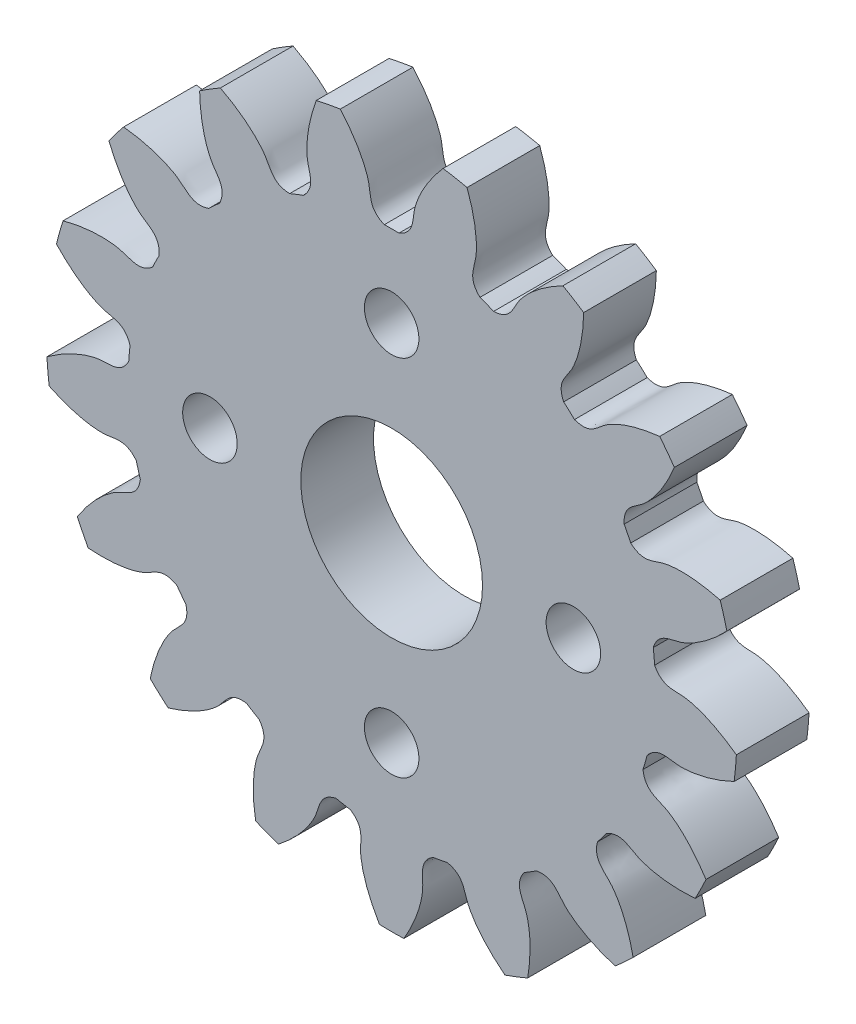
SolidWorks part; units mm, degrees
ref_plane "前视基准面" through (0, 0, 0) normal (0, 0, 1) x (1, 0, 0)
ref_plane "上视基准面" through (0, 0, 0) normal (0, 1, 0) x (1, 0, 0)
ref_plane "右视基准面" through (0, 0, 0) normal (1, 0, 0) x (0, 0, -1)
sketch "草图1" plane through (0, 0, 0) normal (0, 0, 1) x (1, 0, 0)
  circle A0 centre (0, 0) radius 19
extrude "凸台-拉伸1" add sketch "草图1" along normal blind 4
ref_axis "基准轴1" through (0, 0, -0.2) along (0, 0, 1)
sketch "草图2" plane through (0, 0, 0) normal (0, 0, 1) x (1, 0, 0)
  line L0 (0, 0) -> (0, 19) construction
  circle A0 centre (0, 0) radius 19 construction
  arc A1 (0.4034, 14.4944) -> (-0.4034, 14.4944) centre (0, 0) ccw
  arc A2 (6.2313, 21.4814) -> (-6.2313, 21.4814) centre (0, 0) ccw
  spline S0 degree 3 poles (0.4034, 14.4944) (1.2558, 14.8496) (1.1324, 15.5096) (1.2766, 16.1296) (1.29, 16.1823) (1.306, 16.2408) (1.3251, 16.3052) (1.3474, 16.3752) (1.3731, 16.4508) (1.4025, 16.5319) (1.4359, 16.6184) (1.4733, 16.7101) (1.5152, 16.8068) (1.5616, 16.9086) (1.6128, 17.0151) (1.669, 17.1264) (1.7304, 17.2421) (1.7972, 17.3621) (1.8696, 17.4863) (1.9478, 17.6145) (2.032, 17.7465) (2.1224, 17.8821) (2.2191, 18.0211) (2.3223, 18.1634) (2.4322, 18.3086) (2.5489, 18.4566) (2.6727, 18.6072) (2.8035, 18.7601) (2.9417, 18.9152) (3.0873, 19.0722) (3.2404, 19.2308) (3.4012, 19.3908) (3.5698, 19.552) (3.7462, 19.7141) (3.9307, 19.8769) (4.1233, 20.0401) (4.324, 20.2035) (4.533, 20.3667) (4.7503, 20.5295) (4.9761, 20.6917) (5.2103, 20.853) (5.453, 21.0131) (5.7916, 21.2269) (6.0532, 21.3811) (6.2313, 21.4814) knots 0 0 0 0 0.193883 0.199024 0.204851 0.211363 0.21856 0.226443 0.235011 0.244265 0.254205 0.264829 0.27614 0.288136 0.300817 0.314184 0.328236 0.342973 0.358397 0.374505 0.391299 0.408779 0.426944 0.445795 0.465331 0.485552 0.506459 0.528051 0.550329 0.573293 0.596941 0.621276 0.646296 0.672001 0.698392 0.725468 0.753229 0.781677 0.810809 0.840627 0.871131 0.90232 0.934195 1 1 1 1
  spline S1 degree 3 poles (-0.4034, 14.4944) (-1.2558, 14.8496) (-1.1324, 15.5096) (-1.2766, 16.1296) (-1.29, 16.1823) (-1.306, 16.2408) (-1.3251, 16.3052) (-1.3474, 16.3752) (-1.3731, 16.4508) (-1.4025, 16.5319) (-1.4359, 16.6184) (-1.4733, 16.7101) (-1.5152, 16.8068) (-1.5616, 16.9086) (-1.6128, 17.0151) (-1.669, 17.1264) (-1.7304, 17.2421) (-1.7972, 17.3621) (-1.8696, 17.4863) (-1.9478, 17.6145) (-2.032, 17.7465) (-2.1224, 17.8821) (-2.2191, 18.0211) (-2.3223, 18.1634) (-2.4322, 18.3086) (-2.5489, 18.4566) (-2.6727, 18.6072) (-2.8035, 18.7601) (-2.9417, 18.9152) (-3.0873, 19.0722) (-3.2404, 19.2308) (-3.4012, 19.3908) (-3.5698, 19.552) (-3.7462, 19.7141) (-3.9307, 19.8769) (-4.1233, 20.0401) (-4.324, 20.2035) (-4.533, 20.3667) (-4.7503, 20.5295) (-4.9761, 20.6917) (-5.2103, 20.853) (-5.453, 21.0131) (-5.7916, 21.2269) (-6.0532, 21.3811) (-6.2313, 21.4814) knots 0 0 0 0 0.193883 0.199024 0.204851 0.211363 0.21856 0.226443 0.235011 0.244265 0.254205 0.264829 0.27614 0.288136 0.300817 0.314184 0.328236 0.342973 0.358397 0.374505 0.391299 0.408779 0.426944 0.445795 0.465331 0.485552 0.506459 0.528051 0.550329 0.573293 0.596941 0.621276 0.646296 0.672001 0.698392 0.725468 0.753229 0.781677 0.810809 0.840627 0.871131 0.90232 0.934195 1 1 1 1
extrude "切除-拉伸1" cut sketch "草图2" along normal through all
pattern_circular "阵列(圆周)1" count 17 every 21.176 about axis through (0, 0, -0.2) along (0, 0, 1) of "切除-拉伸1"
sketch "草图3" plane through (0, 0, 0) normal (0, 0, 1) x (1, 0, 0)
  circle A0 centre (0, 0) radius 17 construction
  dimension "Dn" = 34
sketch "草图4" plane through (0, 0, 4) normal (0, 0, 1) x (1, 0, 0)
  circle A0 centre (0, 0) radius 5
  dimension "D1" = 10
extrude "切除-拉伸2" cut sketch "草图4" against normal blind 10
sketch "草图5" plane through (0, 0, 4) normal (0, 0, 1) x (1, 0, 0)
  circle A0 centre (0, 10) radius 1.5
  circle A1 centre (10, 0) radius 1.5
  circle A2 centre (0, -10) radius 1.5
  circle A3 centre (-10, 0) radius 1.5
  point P2 (0, 0)
  point P3 (0, 0)
  point P4 (0, 0)
  point P11 (0, 0)
  dimension "D2" = 20
  dimension "D3" = 3
  dimension "D1" = 4
extrude "切除-拉伸3" cut sketch "草图5" against normal blind 10
